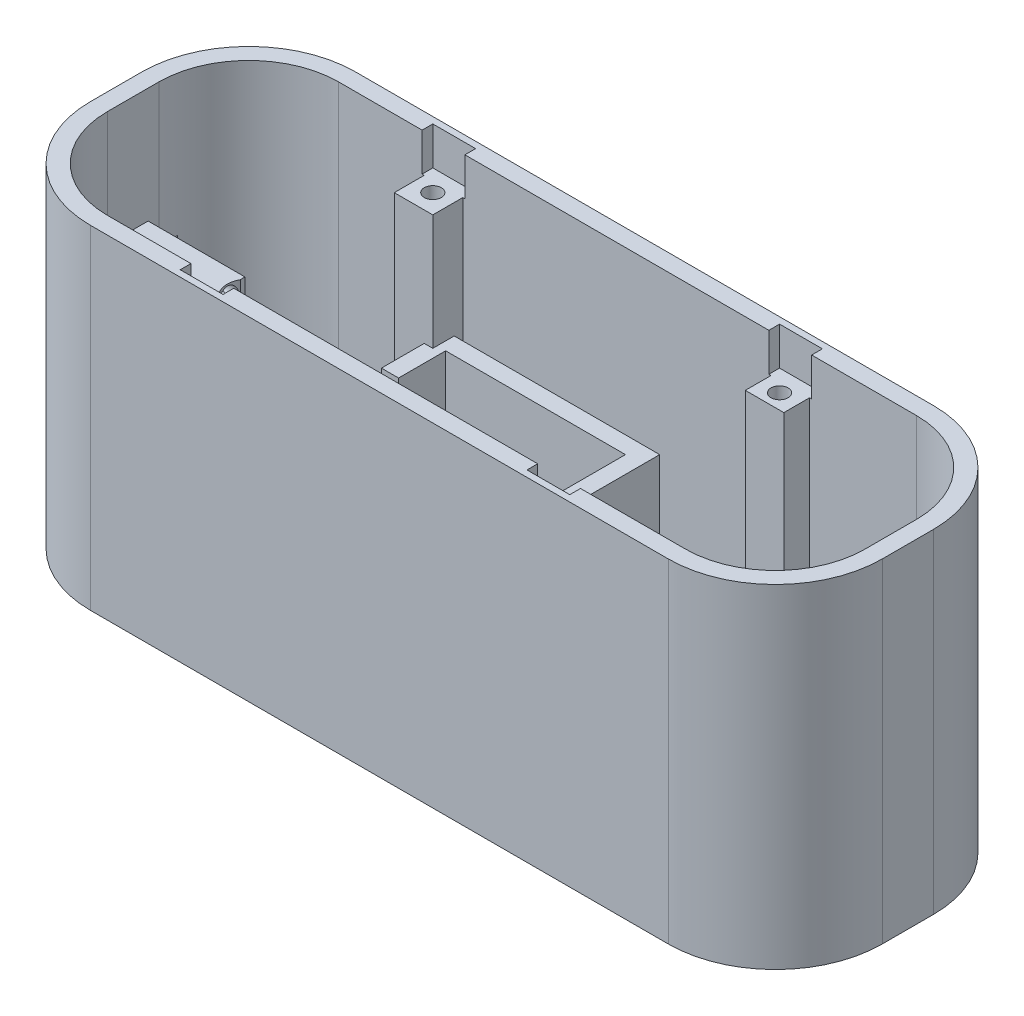
SolidWorks part; units mm, degrees
ref_plane "Front Plane" through (0, 0, 0) normal (0, 0, 1) x (1, 0, 0)
ref_plane "Top Plane" through (0, 0, 0) normal (0, 1, 0) x (1, 0, 0)
ref_plane "Right Plane" through (0, 0, 0) normal (1, 0, 0) x (0, 0, -1)
sketch "Sketch1" plane through (0, 0, 0) normal (0, 1, 0) x (1, 0, 0)
  line L1 (0, 0) -> (185, 0)
  line L2 (0, 0) -> (0, 62)
  line L3 (0, 62) -> (185, 62)
  line L4 (185, 0) -> (185, 62)
  dimension "D1" = 185
  dimension "D2" = 62
extrude "Boss-Extrude1" add sketch "Sketch1" along normal blind 80
fillet "Fillet1" radius 25 4 edges at (185, 40, -62) (185, 40, 0) (0, 40, -62) (0, 40, 0)
ref_plane "Plane1" through (0, 77, 0) normal (0, 1, 0) x (1, 0, 0)
sketch "Sketch7" plane through (0, 77, 0) normal (0, 1, 0) x (1, 0, 0)
  line L0 (25, 58) -> (160, 58)
  line L1 (25, 4) -> (160, 4)
  line L2 (181, 37) -> (181, 25)
  line L3 (4, 37) -> (4, 25)
  line L5 (185, 25) -> (185, 37) construction
  arc A1 (25, 58) -> (4, 37) centre (25, 37) ccw
  arc A2 (25, 4) -> (4, 25) centre (25, 25) cw
  arc A3 (160, 4) -> (181, 25) centre (160, 25) ccw
  arc A4 (160, 58) -> (181, 37) centre (160, 37) cw
  dimension "D1" = 4
extrude "Cut-Extrude6" cut sketch "Sketch7" against normal blind 74
sketch "Sketch19" plane through (0, 0, 0) normal (0, -1, 0) x (1, 0, 0)
  line L0 (0, -37) -> (0, -25) construction
  line L1 (160, -62) -> (25, -62) construction
  circle A0 centre (31, -31) radius 22.5
  circle A1 centre (31, -31) radius 5
  dimension "D1" = 45
  dimension "D4" = 10
  dimension "D2" = 31
  dimension "D3" = 31
extrude "Boss-Extrude7" add sketch "Sketch19" against normal blind 7
sketch "Sketch25" plane through (0, 0, 0) normal (-1, 0, 0) x (0, 0, 1)
  line L0 (-37, 80) -> (-25, 80) construction
  line L1 (-41, 44) -> (-21, 44)
  line L2 (-41, 44) -> (-41, 36)
  line L3 (-41, 36) -> (-21, 36)
  line L4 (-21, 44) -> (-21, 36)
  line L5 (-25, 0) -> (-25, 80) construction
  point P4 (-31, 44)
  point P7 (-31, 80)
  point P8 (-21, 40)
  point P11 (-25, 40)
  dimension "D1" = 8
  dimension "D2" = 20
extrude "Cut-Extrude16" cut sketch "Sketch25" against normal blind 14
sketch "Sketch27" plane through (0, 77, 0) normal (0, 1, 0) x (1, 0, 0)
  line L0 (4.02, 37) -> (4.02, 25)
  line L3 (31, 31) -> (197.2271, 31) construction
  line L4 (31, 73.5576) -> (197.2271, 73.5576)
  line L5 (31, -11.5576) -> (197.2271, -11.5576)
  line L6 (25, 57.98) -> (160, 57.98)
  line L7 (25, 4.02) -> (160, 4.02)
  line L8 (180.98, 37) -> (180.98, 25)
  line L9 (25, 0) -> (160, 0) construction
  arc A2 (31, 73.5576) -> (31, -11.5576) centre (31, 31) ccw
  arc A3 (197.2271, -11.5576) -> (197.2271, 73.5576) centre (197.2271, 31) ccw
  arc A4 (25, 57.98) -> (4.02, 37) centre (25, 37) ccw
  arc A5 (25, 4.02) -> (4.02, 25) centre (25, 25) cw
  arc A6 (180.98, 25) -> (160, 4.02) centre (160, 25) cw
  arc A7 (160, 57.98) -> (180.98, 37) centre (160, 37) cw
  point P10 (114.1135, 31)
  dimension "D1" = 4.02
extrude "Cut-Extrude21" cut sketch "Sketch27" against normal blind 0.1
sketch "Sketch28" plane through (0, 0, 0) normal (0, -1, 0) x (1, 0, 0)
  line L0 (25, 0) -> (160, 0)
  line L1 (185, -25) -> (185, -37)
  line L2 (160, -62) -> (25, -62)
  line L3 (0, -37) -> (0, -25)
  arc A0 (0, -25) -> (25, 0) centre (25, -25) cw
  arc A1 (0, -37) -> (25, -62) centre (25, -37) ccw
  arc A2 (185, -37) -> (160, -62) centre (160, -37) cw
  arc A3 (160, 0) -> (185, -25) centre (160, -25) cw
extrude "Boss-Extrude10" add sketch "Sketch28" along normal blind 1
sketch "Sketch39" plane through (0, 7, 0) normal (0, 1, 0) x (1, 0, 0)
  circle A0 centre (196, 31) radius 5
  dimension "D1" = 10
sketch "Sketch32" plane through (0, -1, 0) normal (0, -1, 0) x (1, 0, 0)
  line L0 (98, -10) -> (56, -52) construction
  line L1 (56, -10) -> (98, -10)
  line L2 (56, -10) -> (56, -21)
  line L3 (56, -52) -> (98, -52)
  line L4 (98, -10) -> (98, -52)
  line L5 (185, -37) -> (185, -25) construction
  line L8 (56, -41) -> (56, -52)
  line L9 (52, -6) -> (102, -6)
  line L10 (52, -6) -> (52, -21)
  line L11 (52, -56) -> (102, -56)
  line L12 (102, -6) -> (102, -56)
  line L13 (52, -21) -> (56, -21)
  line L15 (52, -41) -> (56, -41)
  line L17 (52, -41) -> (52, -56)
  line L18 (-11.1054, -31) -> (255.1636, -31) construction
  line L19 (160, 0) -> (25, 0) construction
  line L20 (25, -62) -> (160, -62) construction
  point P6 (77, -31)
  dimension "D1" = 4
  dimension "D2" = 4
  dimension "D3" = 4
  dimension "D4" = 42
  dimension "D5" = 42
  dimension "D6" = 15
  dimension "D7" = 108
extrude "Boss-Extrude12" add sketch "Sketch32" against normal blind 42
sketch "Sketch30" plane through (0, 77, 0) normal (0, 1, 0) x (1, 0, 0)
  line L0 (160, 62) -> (25, 62) construction
  line L1 (25, 0) -> (160, 0) construction
  line L2 (0, 37) -> (0, 25) construction
  line L3 (185, 25) -> (185, 37) construction
  line L4 (45, 11) -> (54, 11)
  line L5 (45, 60) -> (54, 60)
  line L6 (45, 60) -> (45, 51)
  line L7 (45, 51) -> (54, 51)
  line L8 (54, 60) -> (54, 51)
  line L9 (45, 60) -> (54, 51) construction
  line L10 (45, 51) -> (54, 60) construction
  line L11 (45, 11) -> (45, 2)
  line L12 (45, 2) -> (54, 2)
  line L13 (54, 11) -> (54, 2)
  line L14 (45, 11) -> (54, 2) construction
  line L15 (45, 2) -> (54, 11) construction
  line L16 (126, 60) -> (135, 60)
  line L17 (126, 60) -> (126, 52)
  line L18 (126, 52) -> (135, 52)
  line L19 (135, 60) -> (135, 52)
  line L22 (126, 10) -> (135, 10)
  line L23 (126, 10) -> (126, 2)
  line L24 (126, 2) -> (135, 2)
  line L25 (135, 10) -> (135, 2)
  circle A4 centre (49.5, 55.5) radius 2
  circle A5 centre (49.5, 6.5) radius 2
  circle A6 centre (130.5, 55.5) radius 2
  circle A7 centre (130.5, 6.5) radius 2
  point P33 (130.5, 10)
  point P35 (130.5, 52)
  dimension "D3" = 9
  dimension "D11" = 2
  dimension "D5" = 2
  dimension "D2" = 4
  dimension "D6" = 9
  dimension "D7" = 9
  dimension "D10" = 8
  dimension "D12" = 45
  dimension "D13" = 50
extrude "Boss-Extrude11" add sketch "Sketch30" against normal blind 20
extrude "Cut-Extrude27" cut sketch "Sketch1<3>" against normal blind 3 from surface starting at face at (92.5, 80, -31)
sketch "Sketch1<3>" plane through (0, 0, 0) normal (0, 1, 0) x (1, 0, 0) same geometry as "Sketch1"
extrude "Boss-Extrude13" add sketch "Sketch30<3>" against normal up to next
sketch "Sketch30<3>" plane through (0, 77, 0) normal (0, 1, 0) x (1, 0, 0) same geometry as "Sketch30"
extrude "Cut-Extrude29" cut sketch "Sketch30<6>" against normal blind 9
sketch "Sketch30<6>" plane through (0, 77, 0) normal (0, 1, 0) x (1, 0, 0) same geometry as "Sketch30"
sketch "Sketch34" plane through (0, -1, 0) normal (0, -1, 0) x (1, 0, 0)
  circle A0 centre (31, -31) radius 20.1
  dimension "D1" = 40.2
extrude "Cut-Extrude30" cut sketch "Sketch34" against normal blind 3.5 contours A0 region at (31, -1, -31)
sketch "Sketch35" plane through (0, 0, 0) normal (-1, 0, 0) x (0, 0, 1)
  line L0 (-31, 47.5) -> (-31, 32.5) construction
  line L1 (-37, 76.9) -> (-37, 44) construction
  line L2 (-25, 44) -> (-25, 76.9) construction
  line L3 (-25, 44) -> (-37, 44) construction
  line L5 (-34.5, 45) -> (-27.5, 45)
  line L6 (-34.5, 45) -> (-34.5, 50)
  line L7 (-34.5, 50) -> (-27.5, 50)
  line L8 (-27.5, 45) -> (-27.5, 50)
  line L9 (-34.5, 45) -> (-27.5, 50) construction
  line L10 (-34.5, 50) -> (-27.5, 45) construction
  line L11 (-34.5, 30) -> (-27.5, 30)
  line L12 (-34.5, 30) -> (-34.5, 35)
  line L13 (-34.5, 35) -> (-27.5, 35)
  line L14 (-27.5, 30) -> (-27.5, 35)
  line L15 (-34.5, 30) -> (-27.5, 35) construction
  line L16 (-34.5, 35) -> (-27.5, 30) construction
  circle A0 centre (-31, 47.5) radius 2.1
  circle A1 centre (-31, 32.5) radius 2.1
  dimension "D1" = 4.2
  dimension "D2" = 3.5
  dimension "D3" = 15
  dimension "D4" = 5
  dimension "D5" = 7
extrude "Boss-Extrude14" add sketch "Sketch35" against normal blind 26.6178
extrude "Cut-Extrude31" cut sketch "Sketch35<2>" against normal blind 10 contours A0 | A1 region at (0, 47.5, -31) region at (0, 32.5, -31)
sketch "Sketch35<2>" plane through (0, 0, 0) normal (-1, 0, 0) x (0, 0, 1) same geometry as "Sketch35"
sketch "Sketch36" plane through (0, 3, 0) normal (0, 1, 0) x (1, 0, 0)
  line L1 (102, 58) -> (160, 58)
  line L2 (102, 58) -> (102, 4)
  line L3 (102, 4) -> (160, 4)
  line L6 (102, 6) -> (102, 56) construction
  line L7 (135, 4) -> (160, 4) construction
  line L8 (160, 58) -> (135, 58) construction
  line L9 (181, 25) -> (181, 37)
  arc A0 (160, 4) -> (181, 25) centre (160, 25) ccw
  arc A1 (181, 37) -> (160, 58) centre (160, 37) ccw
extrude "Boss-Extrude15" add sketch "Sketch36" along normal blind 4
sketch "Sketch37" plane through (0, -1, 0) normal (0, -1, 0) x (1, 0, 0)
  line L0 (135.75, -31) -> (172.25, -31) construction
  line L1 (160, 0) -> (25, 0) construction
  line L2 (25, -62) -> (160, -62) construction
  line L3 (185, -37) -> (185, -25) construction
  circle A0 centre (135.75, -31) radius 5.1
  circle A1 centre (172.25, -31) radius 5.1
  circle A2 centre (135.75, -31) radius 2.6
  circle A3 centre (172.25, -31) radius 2.6
  point P8 (154, -31)
  dimension "D2" = 10.2
  dimension "D3" = 31
  dimension "D4" = 5.2
  dimension "D1" = 36.5
extrude "Cut-Extrude32" cut sketch "Sketch37" against normal blind 5
extrude "Cut-Extrude33" cut sketch "Sketch37<2>" against normal blind 45 contours A2 | A3 region at (135.75, -1, -31) region at (172.25, -1, -31)
sketch "Sketch37<2>" plane through (0, -1, 0) normal (0, -1, 0) x (1, 0, 0) same geometry as "Sketch37"
extrude "Cut-Extrude34" cut sketch "Sketch30<7>" against normal up to surface (74 mm away) contours A6 | A7 region at (130.5, 77, -55.5) region at (130.5, 77, -6.5) up to face at (47.6279, 3, -31)
sketch "Sketch30<7>" plane through (0, 77, 0) normal (0, 1, 0) x (1, 0, 0) same geometry as "Sketch30"
extrude "Cut-Extrude36" cut sketch "Sketch19<3>" along normal through all both and the other way through all contours A1 region at (31, 0, -31)
sketch "Sketch19<3>" plane through (0, 0, 0) normal (0, -1, 0) x (1, 0, 0) same geometry as "Sketch19"
sketch "Sketch40" plane through (0, 76.9, 0) normal (0, 1, 0) x (1, 0, 0)
  line L1 (44.5, 50.5) -> (54.5, 50.5)
  line L2 (44.5, 50.5) -> (44.5, 60.5)
  line L3 (44.5, 60.5) -> (54.5, 60.5)
  line L4 (54.5, 50.5) -> (54.5, 60.5)
  line L5 (44.5, 50.5) -> (54.5, 60.5) construction
  line L6 (44.5, 60.5) -> (54.5, 50.5) construction
  line L7 (125.5, 50.5) -> (135.5, 50.5)
  line L8 (125.5, 50.5) -> (125.5, 60.5)
  line L9 (125.5, 60.5) -> (135.5, 60.5)
  line L10 (135.5, 50.5) -> (135.5, 60.5)
  line L11 (125.5, 50.5) -> (135.5, 60.5) construction
  line L12 (125.5, 60.5) -> (135.5, 50.5) construction
  line L13 (125.5, 11.5) -> (135.5, 11.5)
  line L14 (125.5, 11.5) -> (125.5, 1.5)
  line L15 (125.5, 1.5) -> (135.5, 1.5)
  line L16 (135.5, 11.5) -> (135.5, 1.5)
  line L17 (125.5, 11.5) -> (135.5, 1.5) construction
  line L18 (125.5, 1.5) -> (135.5, 11.5) construction
  line L19 (44.5, 11.5) -> (54.5, 11.5)
  line L20 (44.5, 11.5) -> (44.5, 1.5)
  line L21 (44.5, 1.5) -> (54.5, 1.5)
  line L22 (54.5, 11.5) -> (54.5, 1.5)
  line L23 (44.5, 11.5) -> (54.5, 1.5) construction
  line L24 (44.5, 1.5) -> (54.5, 11.5) construction
  point P0 (49.5, 55.5)
  point P6 (130.5, 55.5)
  point P12 (130.5, 6.5)
  point P18 (49.5, 6.5)
  dimension "D1" = 10
extrude "Cut-Extrude37" cut sketch "Sketch40" against normal up to surface (8.9 mm away) from offset 0 up to face at (49.5, 68, -53.5)
sketch "Sketch41" plane through (0, 7, 0) normal (0, 1, 0) x (1, 0, 0)
  line L0 (59.1378, 41) -> (52, 41)
  line L1 (52, 41) -> (52, 48.2988)
  line L3 (52, 48.2988) -> (44.0239, 51)
  line L4 (44.0239, 51) -> (40, 55.5499)
  line L5 (40, 55.5499) -> (40, 8.1692)
  line L6 (40, 8.1692) -> (52, 15.5854)
  line L7 (52, 15.5854) -> (52, 21)
  line L8 (52, 21) -> (56, 21)
  line L9 (56, 21) -> (59.1378, 41)
  line L10 (52, 51) -> (52, 41) construction
  line L11 (52, 11) -> (52, 21) construction
  dimension "D1" = 12
extrude "Cut-Extrude38" cut sketch "Sketch41" against normal up to surface (4 mm away) up to face at (47.6279, 3, -31)
